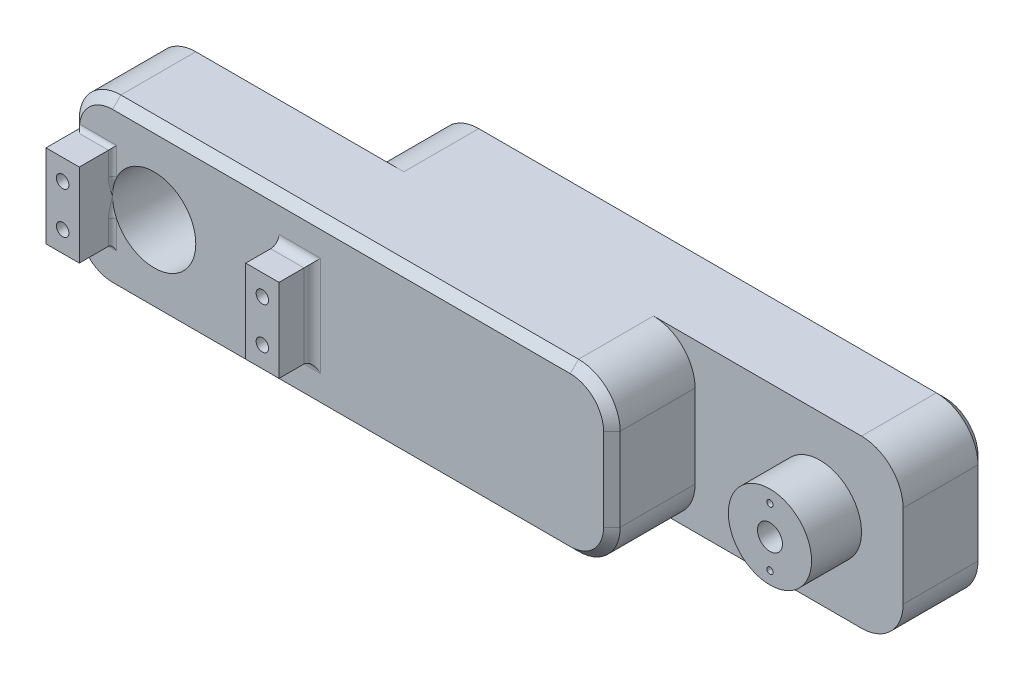
SolidWorks part; units mm, degrees
ref_plane "Front Plane" through (0, 0, 0) normal (0, 0, 1) x (1, 0, 0)
ref_plane "Top Plane" through (0, 0, 0) normal (0, 1, 0) x (1, 0, 0)
ref_plane "Right Plane" through (0, 0, 0) normal (1, 0, 0) x (0, 0, -1)
sketch "Sketch1" plane through (0, 0, 0) normal (0, 0, 1) x (1, 0, 0)
  line L1 (0, 0) -> (180, 0)
  line L2 (0, 0) -> (0, 40)
  line L3 (0, 40) -> (180, 40)
  line L4 (180, 0) -> (180, 40)
  circle A1 centre (20, 20) radius 10
  dimension "D6" = 20
  dimension "D7" = 20
  dimension "D8" = 20
  dimension "D1" = 180
  dimension "D2" = 40
extrude "Boss-Extrude1" add sketch "Sketch1" along normal blind 40
ref_plane "Plane1" through (0, 0, 20) normal (0, 0, 1) x (1, 0, 0)
sketch "Sketch4" plane through (0, 40, 0) normal (0, 1, 0) x (1, 0, 0)
  line L0 (-22, -20) -> (22, -20) construction
  line L1 (180, -40) -> (130, -40)
  line L2 (180, -40) -> (180, -20)
  line L3 (180, -20) -> (130, -20)
  line L4 (130, -40) -> (130, -20)
  dimension "D1" = 50
extrude "Cut-Extrude3" cut sketch "Sketch4" against normal blind 50
sketch "Sketch5" plane through (0, 40, 0) normal (0, 1, 0) x (1, 0, 0)
  line L0 (-22, -20) -> (22, -20) construction
  line L1 (0, 0) -> (50, 0)
  line L2 (0, 0) -> (0, -20)
  line L3 (0, -20) -> (50, -20)
  line L4 (50, 0) -> (50, -20)
  dimension "D1" = 50
extrude "Cut-Extrude4" cut sketch "Sketch5" against normal blind 50
sketch "Sketch6" plane through (0, 0, 20) normal (0, 0, 1) x (1, 0, 0)
  line L0 (180, 0) -> (130, 0) construction
  line L1 (180, 0) -> (180, 40) construction
  circle A0 centre (160, 20) radius 10
  dimension "D1" = 20
  dimension "D2" = 20
  dimension "D3" = 20
extrude "Boss-Extrude2" add sketch "Sketch6" along normal blind 12
fillet "Fillet1" radius 10 8 edges at (50, 0, 10) (50, 40, 10) (180, 0, 10) (180, 40, 10) (130, 0, 30) (130, 40, 30) (0, 0, 30) (0, 40, 30)
chamfer "Chamfer1" distance 2 angle 45 16 edges at (177.0711, 2.9289, 0) (180, 20, 0) (177.0711, 37.0711, 0) (115, 40, 0) (52.9289, 37.0711, 0) (50, 20, 0) (52.9289, 2.9289, 0) (115, 0, 0) (2.9289, 2.9289, 40) (0, 20, 40) (2.9289, 37.0711, 40) (65, 40, 40) (127.0711, 37.0711, 40) (130, 20, 40) (127.0711, 2.9289, 40) (65, 0, 40)
sketch "Sketch7" plane through (0, 0, 40) normal (0, 0, 1) x (1, 0, 0)
  line L0 (2, 30) -> (2, 10) construction
  line L1 (2, 30) -> (10, 30)
  line L2 (2, 30) -> (2, 10)
  line L3 (2, 10) -> (10, 10)
  line L4 (10, 30) -> (10, 10)
  dimension "D1" = 20
  dimension "D2" = 8
extrude "Boss-Extrude3" add sketch "Sketch7" along normal blind 8
sketch "Sketch8" plane through (0, 0, 48) normal (0, 0, 1) x (1, 0, 0)
  line L0 (10, 30) -> (2, 30) construction
  line L1 (10, 20) -> (10, 30) construction
  circle A0 centre (6, 25) radius 1.5
  dimension "D1" = 3
  dimension "D2" = 5
  dimension "D3" = 4
extrude "Cut-Extrude5" cut sketch "Sketch8" against normal blind 5
pattern_linear "LPattern1" count 2 spacing 10 along (0, -1, 0) of "Cut-Extrude5"
fillet "Fillet2" radius 1 4 edges at (10, 15, 40) (6, 30, 40) (6, 10, 40) (10, 25, 40)
pattern_linear "LPattern2" count 2 spacing 48 along (1, 0, 0) of "Boss-Extrude3", "Cut-Extrude5", "LPattern1"
fillet "Fillet3" radius 2 3 edges at (54, 30, 40) (58, 20, 40) (54, 10, 40)
sketch "Sketch9" plane through (0, 0, 32) normal (0, 0, 1) x (1, 0, 0)
  circle A0 centre (160, 20) radius 3
  dimension "D1" = 6
extrude "Cut-Extrude6" cut sketch "Sketch9" against normal blind 40
sketch "Sketch10" plane through (0, 0, 32) normal (0, 0, 1) x (1, 0, 0)
  line L0 (160, 20) -> (160, 33.0785) construction
  circle A0 centre (160, 27) radius 0.75
  circle A1 centre (160, 20) radius 3 construction
  dimension "D1" = 1.5
  dimension "D2" = 7
extrude "Cut-Extrude7" cut sketch "Sketch10" against normal blind 5
pattern_linear "LPattern3" count 2 spacing 14 along (0, -1, 0) of "Cut-Extrude7"
